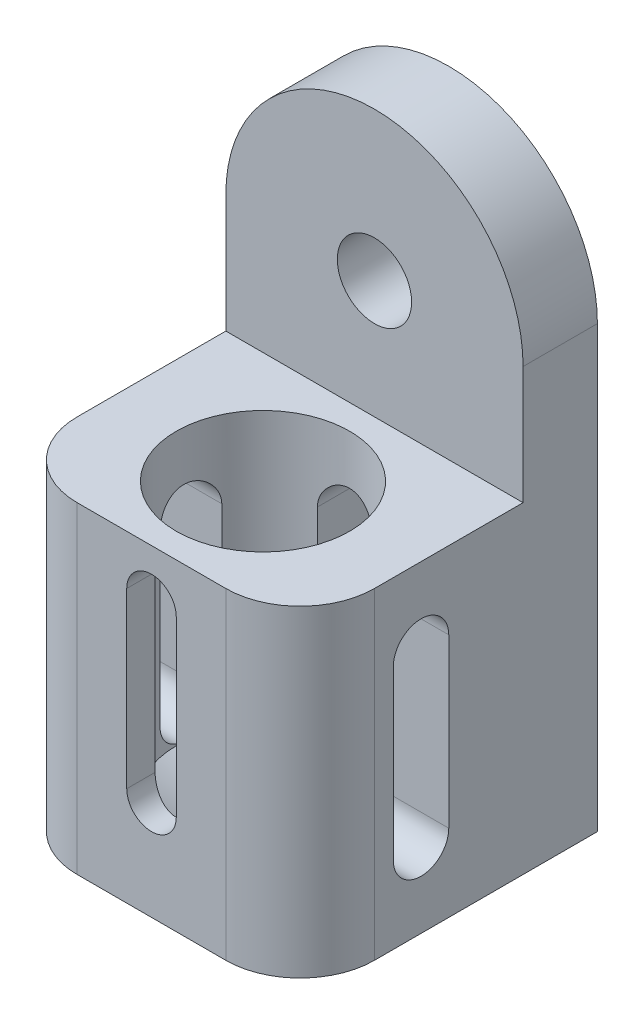
SolidWorks part; units mm, degrees
material "6061-T6 (SS)"
ref_plane "Front Plane" through (0, 0, 0) normal (0, 0, 1) x (1, 0, 0)
ref_plane "Top Plane" through (0, 0, 0) normal (0, 1, 0) x (1, 0, 0)
ref_plane "Right Plane" through (0, 0, 0) normal (1, 0, 0) x (0, 0, -1)
ref_axis "X-axis" through (-88.99, 0, 0) along (1, 0, 0)
ref_axis "Y-axis" through (0, 55, 0) along (0, -1, 0)
ref_axis "Z-axis" through (0, 0, -88.99) along (0, 0, 1)
sketch "Sketch1" plane through (0, 0, 0) normal (0, 1, 0) x (1, 0, 0)
  line L1 (38.1, 28.575) -> (-38.1, 28.575)
  line L2 (38.1, 28.575) -> (38.1, -28.575)
  line L3 (38.1, -28.575) -> (-38.1, -28.575)
  line L4 (-38.1, 28.575) -> (-38.1, -28.575)
  line L5 (38.1, 28.575) -> (-38.1, -28.575) construction
  line L6 (38.1, -28.575) -> (-38.1, 28.575) construction
  point P0 (0, 0)
  dimension "D1" = 76.2
  dimension "D2" = 57.15
extrude "Boss-Extrude1" add sketch "Sketch1" against normal blind 82.55
fillet "Fillet1" radius 19.05 2 edges at (-38.1, -41.275, 28.575) (38.1, -41.275, 28.575)
sketch "Sketch2" plane through (0, 0, 0) normal (0, 1, 0) x (1, 0, 0)
  line L0 (38.1, 28.575) -> (38.1, 47.625)
  line L1 (38.1, 47.625) -> (-38.1, 47.625)
  line L2 (-38.1, 47.625) -> (-38.1, 28.575)
  line L3 (-38.1, 28.575) -> (38.1, 28.575)
  dimension "D1" = 19.05
extrude "Boss-Extrude2" add sketch "Sketch2" against normal blind 82.55
sketch "Sketch6" plane through (0, 0, 0) normal (1, 0, 0) x (0, 0, -1)
  line L0 (2.413, -62.738) -> (2.413, -19.812) construction
  line L1 (-4.699, -62.738) -> (-4.699, -19.812)
  line L2 (9.525, -62.738) -> (9.525, -19.812)
  line L9 (-28.575, -82.55) -> (-28.575, 0) construction
  line L10 (-9.525, -82.55) -> (47.625, -82.55) construction
  arc A0 (-4.699, -62.738) -> (9.525, -62.738) centre (2.413, -62.738) ccw
  arc A1 (9.525, -19.812) -> (-4.699, -19.812) centre (2.413, -19.812) ccw
  point P2 (2.413, -41.275)
  dimension "D1" = 30.988
  dimension "D2" = 19.812
  dimension "D3" = 42.926
extrude "Cut-Extrude1" cut sketch "Sketch6" against normal mid plane 76.2
sketch "Sketch7" plane through (0, 0, 28.575) normal (0, 0, 1) x (1, 0, 0)
  line L0 (0, -12.7) -> (0, -57.15) construction
  line L1 (6.35, -12.7) -> (6.35, -57.15)
  line L2 (-6.35, -12.7) -> (-6.35, -57.15)
  line L3 (-19.05, -82.55) -> (19.05, -82.55) construction
  arc A0 (6.35, -12.7) -> (-6.35, -12.7) centre (0, -12.7) ccw
  arc A1 (-6.35, -57.15) -> (6.35, -57.15) centre (0, -57.15) ccw
  point P2 (0, -34.925)
  dimension "D1" = 44.45
  dimension "D2" = 25.4
  dimension "D3" = 12.7
extrude "Cut-Extrude2" cut sketch "Sketch7" against normal blind 19.05
sketch "Sketch11" plane through (0, 0, -47.625) normal (0, 0, -1) x (-1, 0, 0)
  line L0 (-38.1, 0) -> (-38.1, 30.226)
  line L1 (38.1, 30.226) -> (38.1, 0)
  line L2 (38.1, 0) -> (-38.1, 0)
  arc A0 (-38.1, 30.226) -> (38.1, 30.226) centre (0, 30.226) cw
  dimension "D1" = 30.226
extrude "Boss-Extrude5" add sketch "Sketch11" against normal blind 19.05
hole_wizard "1/4 (0.75) Diameter Hole2" positions "Sketch12" profile "Sketch13" hole size "1/4" standard "ANSI Inch" end condition through all
sketch "Sketch12" plane through (0, 0, -28.575) normal (0, 0, 1) x (1, 0, 0)
  point P0 (0, 30.226)
sketch "Sketch13" plane through (0, 30.226, -28.575) normal (1, 0, 0) x (0, -1, 0)
  line L0 (0, 0) -> (0, 19.05)
  line L1 (0, 19.05) -> (9.525, 19.05)
  line L2 (9.525, 19.05) -> (9.525, 0)
  line L5 (9.525, 0) -> (0, 0)
  line L11 (0, -6.35) -> (0, 107.95) construction
  dimension "Thru Hole Dia." = 19.05
  dimension "Thru Hole Depth" = 19.05
sketch "Sketch14" plane through (0, 0, -47.625) normal (0, 0, -1) x (-1, 0, 0)
  line L0 (0, -19.812) -> (0, -62.738) construction
  line L1 (7.112, -19.812) -> (7.112, -62.738)
  line L2 (-7.112, -19.812) -> (-7.112, -62.738)
  line L3 (-38.1, -82.55) -> (38.1, -82.55) construction
  arc A0 (7.112, -19.812) -> (-7.112, -19.812) centre (0, -19.812) ccw
  arc A1 (-7.112, -62.738) -> (7.112, -62.738) centre (0, -62.738) ccw
  point P2 (0, -41.275)
  dimension "D1" = 14.224
  dimension "D2" = 42.926
  dimension "D3" = 19.812
extrude "Cut-Extrude4" cut sketch "Sketch14" against normal up to next
hole_wizard "1/4 (1.75) Diameter Hole2" positions "Sketch15" profile "Sketch17" hole size "1/4" standard "ANSI Inch"
sketch "Sketch15" plane through (0, 0, 0) normal (0, 1, 0) x (1, 0, 0)
  point P0 (0, 0)
sketch "Sketch17" plane through (0, 0, 0) normal (1, 0, 0) x (0, 0, 1)
  line L0 (0, 0) -> (0, 83.2041)
  line L1 (0, 83.2041) -> (22.225, 69.85)
  line L2 (22.225, 69.85) -> (22.225, 0)
  line L5 (22.225, 0) -> (0, 0)
  line L10 (0, 83.2041) -> (-22.225, 69.85) construction
  line L11 (0, -6.35) -> (0, 107.95) construction
  dimension "Hole Dia." = 44.45
  dimension "Hole Depth" = 69.85
  dimension "Drill Angle" = 118
